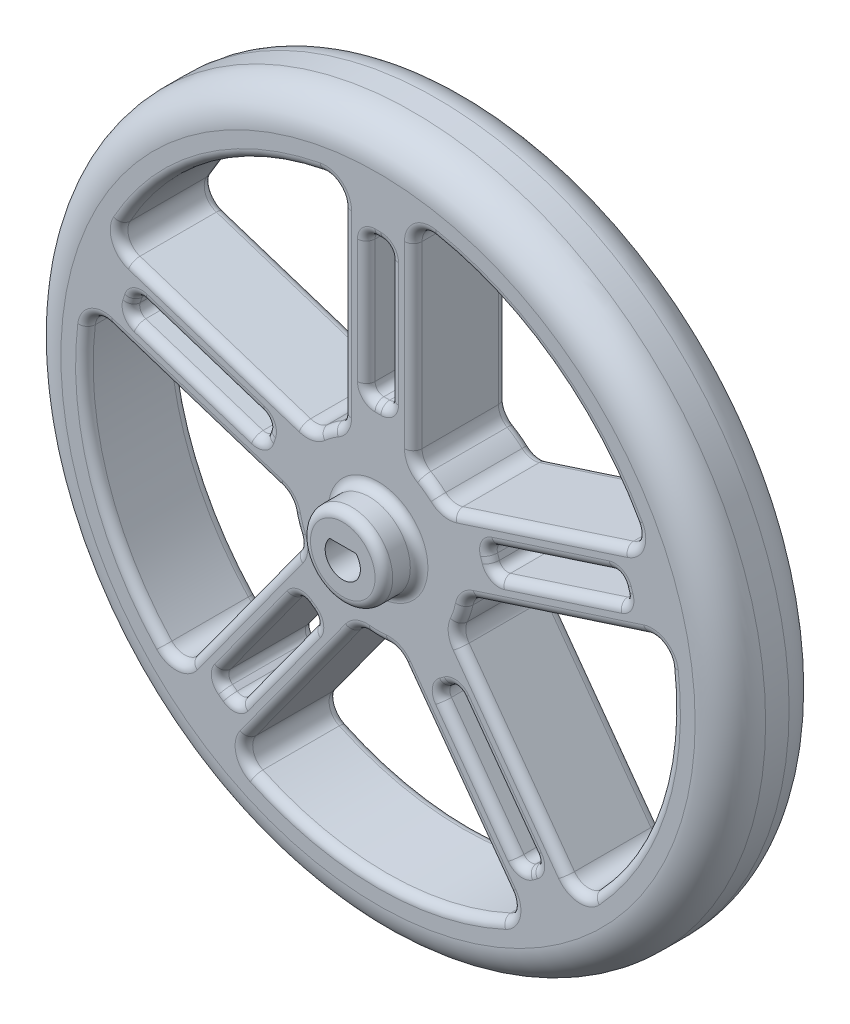
SolidWorks part; units mm, degrees
material "ABS"
ref_plane "Front Plane" through (0, 0, 0) normal (0, 0, 1) x (1, 0, 0)
ref_plane "Top Plane" through (0, 0, 0) normal (0, 1, 0) x (1, 0, 0)
ref_plane "Right Plane" through (0, 0, 0) normal (1, 0, 0) x (0, 0, -1)
sketch "Sketch1" plane through (0, 0, 0) normal (0, 0, 1) x (1, 0, 0)
  line L0 (-1.118, 1) -> (1.118, 1)
  line L1 (-1.5, 0) -> (1.5, 0) construction
  line L2 (0, -30) -> (0, 30) construction
  line L3 (-3, 6.8739) -> (-3, 24.8193)
  line L4 (-1, 10) -> (-1, 22)
  line L5 (-1, 22) -> (1, 22)
  line L6 (-1, 10) -> (1, 10)
  line L7 (1, 10) -> (1, 22)
  line L8 (3, 6.8739) -> (3, 24.8193)
  line L9 (9.8196, 2.1391) -> (21.2323, 5.8473)
  line L10 (9.2015, 4.0412) -> (20.6142, 7.7494)
  line L11 (9.2015, 4.0412) -> (9.8196, 2.1391)
  line L12 (20.6142, 7.7494) -> (21.2323, 5.8473)
  line L13 (7.4645, -0.729) -> (24.5317, 4.8164)
  line L14 (5.6104, 4.9773) -> (22.6776, 10.5228)
  line L15 (5.0688, -8.678) -> (12.1223, -18.3862)
  line L16 (6.6869, -7.5024) -> (13.7403, -17.2106)
  line L17 (6.6869, -7.5024) -> (5.0688, -8.678)
  line L18 (13.7403, -17.2106) -> (12.1223, -18.3862)
  line L19 (1.6133, -7.3244) -> (12.1614, -21.8426)
  line L20 (6.4674, -3.7977) -> (17.0155, -18.3159)
  line L21 (-6.6869, -7.5024) -> (-13.7403, -17.2106)
  line L22 (-5.0688, -8.678) -> (-12.1223, -18.3862)
  line L23 (-5.0688, -8.678) -> (-6.6869, -7.5024)
  line L24 (-12.1223, -18.3862) -> (-13.7403, -17.2106)
  line L25 (-6.4674, -3.7977) -> (-17.0155, -18.3159)
  line L26 (-1.6133, -7.3244) -> (-12.1614, -21.8426)
  line L27 (-9.2015, 4.0412) -> (-20.6142, 7.7494)
  line L28 (-9.8196, 2.1391) -> (-21.2323, 5.8473)
  line L29 (-9.8196, 2.1391) -> (-9.2015, 4.0412)
  line L30 (-21.2323, 5.8473) -> (-20.6142, 7.7494)
  line L31 (-5.6104, 4.9773) -> (-22.6776, 10.5228)
  line L32 (-7.4645, -0.729) -> (-24.5317, 4.8164)
  line L33 (0, 0) -> (3, 6.8739) construction
  circle A0 centre (0, 0) radius 30
  arc A1 (-3, 6.8739) -> (-5.6104, 4.9773) centre (0, 0) ccw
  arc A2 (-1.118, 1) -> (1.118, 1) centre (0, 0) ccw
  arc A3 (-24.5317, 4.8164) -> (-17.0155, -18.3159) centre (0, 0) ccw
  arc A4 (-12.1614, -21.8426) -> (12.1614, -21.8426) centre (0, 0) ccw
  arc A5 (17.0155, -18.3159) -> (24.5317, 4.8164) centre (0, 0) ccw
  arc A6 (22.6776, 10.5228) -> (3, 24.8193) centre (0, 0) ccw
  arc A7 (-3, 24.8193) -> (-22.6776, 10.5228) centre (0, 0) ccw
  arc A8 (5.6104, 4.9773) -> (3, 6.8739) centre (0, 0) ccw
  arc A9 (6.4674, -3.7977) -> (7.4645, -0.729) centre (0, 0) ccw
  arc A10 (-1.6133, -7.3244) -> (1.6133, -7.3244) centre (0, 0) ccw
  arc A11 (-7.4645, -0.729) -> (-6.4674, -3.7977) centre (0, 0) ccw
  point P18 (0, 22)
  point P19 (0, 10)
  point P31 (20.9232, 6.7984)
  point P32 (9.5106, 3.0902)
  point P41 (12.9313, -17.7984)
  point P42 (5.8779, -8.0902)
  point P51 (-12.9313, -17.7984)
  point P52 (-5.8779, -8.0902)
  point P61 (-20.9232, 6.7984)
  point P62 (-9.5106, 3.0902)
  dimension "D1" = 60
  dimension "D2" = 15
  dimension "D3" = 3
  dimension "D5" = 50
  dimension "D9" = 10
  dimension "D4" = 1
  dimension "D6" = 3
  dimension "D7" = 2
  dimension "D8" = 12
  dimension "D10" = 5
extrude "Boss-Extrude1" add sketch "Sketch1" along normal blind 8
sketch "Sketch2" plane through (0, 0, 8) normal (0, 0, 1) x (1, 0, 0)
  line L0 (1.118, 1) -> (-1.118, 1) construction
  line L1 (1.118, 1) -> (-1.118, 1)
  arc A0 (-1.118, 1) -> (1.118, 1) centre (0, 0) ccw construction
  arc A1 (-1.118, 1) -> (1.118, 1) centre (0, 0) ccw
  circle A2 centre (0, 0) radius 3.5
  dimension "D1" = 7
extrude "Boss-Extrude2" add sketch "Sketch2" along normal blind 3
fillet "Fillet1" radius 1.5 20 edges at (-17.0155, -18.3159, 4) (-24.5317, 4.8164, 4) (-7.4645, -0.729, 4) (-6.4674, -3.7977, 4) (-12.1614, -21.8426, 4) (-1.6133, -7.3244, 4) (12.1614, -21.8426, 4) (1.6133, -7.3244, 4) (6.4674, -3.7977, 4) (7.4645, -0.729, 4) (17.0155, -18.3159, 4) (24.5317, 4.8164, 4) (3, 6.8739, 4) (5.6104, 4.9773, 4) (22.6776, 10.5228, 4) (3, 24.8193, 4) (-22.6776, 10.5228, 4) (-3, 24.8193, 4) (-5.6104, 4.9773, 4) (-3, 6.8739, 4)
fillet "Fillet2" radius 0.75 140 edges at (-15.5259, 3.9932, 0) (-20.9232, 6.7984, 0) (-14.9079, 5.8953, 0) (-9.5106, 3.0902, 0) (-5.8779, -8.0902, 0) (5.8779, -8.0902, 0) (20.9232, 6.7984, 0) (9.5106, 3.0902, 0) (-1, 16, 0) (0, 22, 0) (1, 16, 0) (0, 10, 0) (-21.9415, 10.858, 0) (-14.6946, 20.2254, 0) (-3.5463, 24.2229, 0) (-3, 15.4297, 0) (-3.201, 7.0442, 0) (-4.4084, 6.0676, 0) (-5.7103, 5.2211, 0) (-13.7474, 7.6212, 0) (3.5463, 24.2229, 0) (14.6946, 20.2254, 0) (21.9415, 10.858, 0) (13.7474, 7.6212, 0) (5.7103, 5.2211, 0) (4.4084, 6.0676, 0) (3.201, 7.0442, 0) (3, 15.4297, 0) (24.1332, 4.1126, 0) (23.7764, -7.7254, 0) (17.1069, -17.5123, 0) (11.4964, -10.7195, 0) (6.7301, -3.8174, 0) (7.1329, -2.3176, 0) (7.6886, -0.8675, 0) (15.6015, 1.9149, 0) (11.3689, -21.6812, 0) (0, -25, 0) (-11.3689, -21.6812, 0) (-6.6423, -14.2462, 0) (-1.5509, -7.5804, 0) (0, -7.5, 0) (1.5509, -7.5804, 0) (6.6423, -14.2462, 0) (-17.1069, -17.5123, 0) (-23.7764, -7.7254, 0) (-24.1332, 4.1126, 0) (-15.6015, 1.9149, 0) (-7.6886, -0.8675, 0) (-7.1329, -2.3176, 0) (-6.7301, -3.8174, 0) (-11.4964, -10.7195, 0) (-20.9232, 6.7984, 8) (-15.5259, 3.9932, 8) (-9.5106, 3.0902, 8) (-14.9079, 5.8953, 8) (-24.1332, 4.1126, 8) (-23.7764, -7.7254, 8) (-17.1069, -17.5123, 8) (-11.4964, -10.7195, 8) (-6.7301, -3.8174, 8) (-7.1329, -2.3176, 8) (-7.6886, -0.8675, 8) (-15.6015, 1.9149, 8) (-12.9313, -17.7984, 8) (-5.8779, -8.0902, 8) (-11.3689, -21.6812, 8) (0, -25, 8) (11.3689, -21.6812, 8) (6.6423, -14.2462, 8) (1.5509, -7.5804, 8) (0, -7.5, 8) (-1.5509, -7.5804, 8) (-6.6423, -14.2462, 8) (12.9313, -17.7984, 8) (5.8779, -8.0902, 8) (17.1069, -17.5123, 8) (23.7764, -7.7254, 8) (24.1332, 4.1126, 8) (15.6015, 1.9149, 8) (7.6886, -0.8675, 8) (7.1329, -2.3176, 8) (6.7301, -3.8174, 8) (11.4964, -10.7195, 8) (20.9232, 6.7984, 8) (9.5106, 3.0902, 8) (21.9415, 10.858, 8) (14.6946, 20.2254, 8) (3.5463, 24.2229, 8) (3, 15.4297, 8) (3.201, 7.0442, 8) (4.4084, 6.0676, 8) (5.7103, 5.2211, 8) (13.7474, 7.6212, 8) (0, 22, 8) (-1, 16, 8) (0, 10, 8) (1, 16, 8) (-3.5463, 24.2229, 8) (-14.6946, 20.2254, 8) (-21.9415, 10.858, 8) (-13.7474, 7.6212, 8) (-5.7103, 5.2211, 8) (-4.4084, 6.0676, 8) (-3.201, 7.0442, 8) (-3, 15.4297, 8) (21.2323, 5.8473, 4) (15.5259, 3.9932, 8) (9.8196, 2.1391, 4) (15.5259, 3.9932, 0) (9.2015, 4.0412, 4) (14.9079, 5.8953, 8) (20.6142, 7.7494, 4) (14.9079, 5.8953, 0) (12.1223, -18.3862, 4) (8.5955, -13.5321, 8) (5.0688, -8.678, 4) (8.5955, -13.5321, 0) (6.6869, -7.5024, 4) (10.2136, -12.3565, 8) (13.7403, -17.2106, 4) (10.2136, -12.3565, 0) (-13.7403, -17.2106, 4) (-10.2136, -12.3565, 8) (-6.6869, -7.5024, 4) (-10.2136, -12.3565, 0) (-5.0688, -8.678, 4) (-8.5955, -13.5321, 8) (-12.1223, -18.3862, 4) (-8.5955, -13.5321, 0) (1, 22, 4) (1, 10, 4) (-1, 10, 4) (-1, 22, 4) (-9.8196, 2.1391, 4) (-21.2323, 5.8473, 4) (-20.6142, 7.7494, 4) (-9.2015, 4.0412, 4) (3.5, 0, 11) (3.5, 0, 8)
fillet "Fillet3" radius 3 2 edges at (30, 0, 0) (30, 0, 8)
